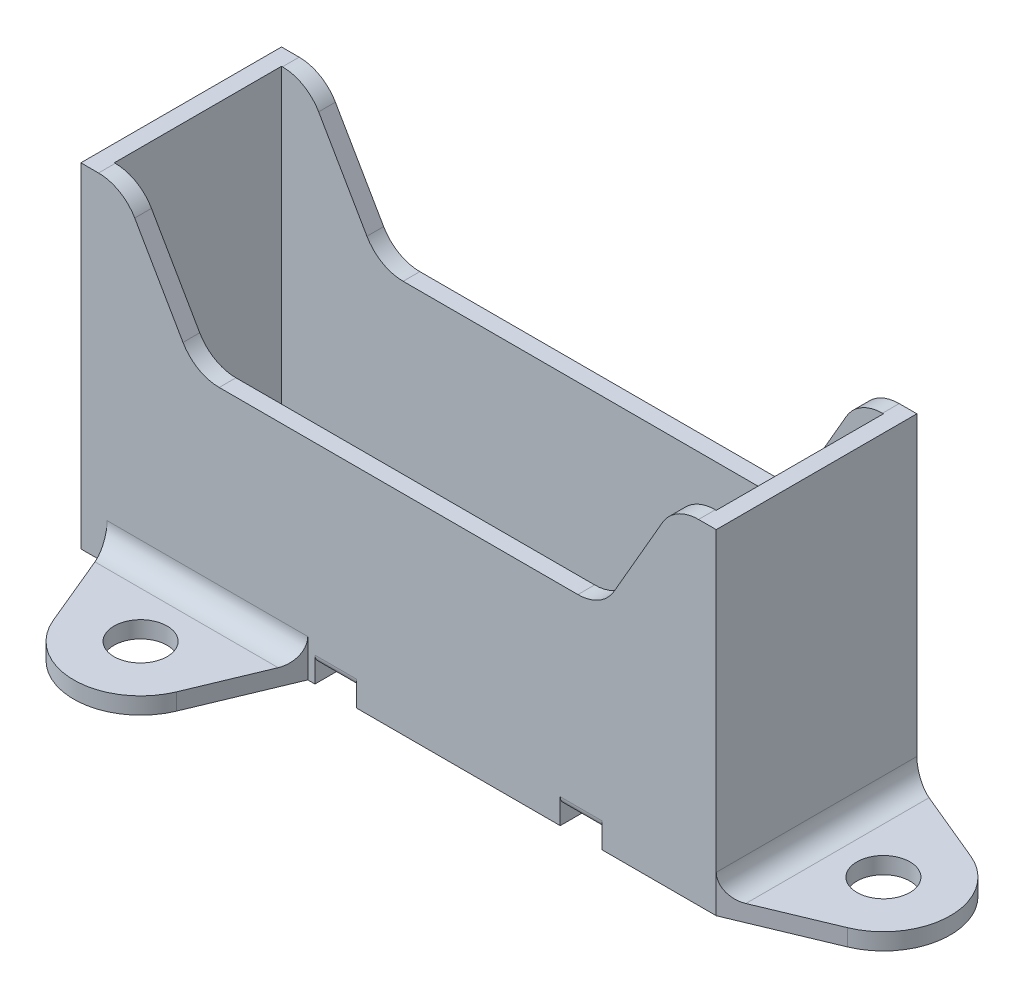
SolidWorks part; units mm, degrees
ref_plane "Front Plane" through (0, 0, 0) normal (0, 0, 1) x (1, 0, 0)
ref_plane "Top Plane" through (0, 0, 0) normal (0, 1, 0) x (1, 0, 0)
ref_plane "Right Plane" through (0, 0, 0) normal (1, 0, 0) x (0, 0, -1)
sketch "Sketch15" plane through (0, 0, 0) normal (0, 1, 0) x (1, 0, 0)
  line L0 (-38, -12) -> (-38, 12)
  line L1 (-36, -10) -> (36, -10)
  line L2 (-36, -10) -> (-36, 10)
  line L3 (-36, 10) -> (36, 10)
  line L4 (36, -10) -> (36, 10)
  line L5 (-36, -10) -> (36, 10) construction
  line L6 (-36, 10) -> (36, -10) construction
  line L7 (-38, 12) -> (38, 12)
  line L8 (38, -12) -> (38, 12)
  line L9 (-38, -12) -> (38, -12)
  point P0 (0, 0)
  dimension "D1" = 72
  dimension "D2" = 20
  dimension "D3" = 2
extrude "Boss-Extrude8" add sketch "Sketch15" along normal blind 38
sketch "Sketch18" plane through (0, 0, 0) normal (0, -1, 0) x (1, 0, 0)
  line L0 (-38, 12) -> (-34.8585, 12)
  line L1 (38, 12) -> (49.0769, 7.3846)
  line L2 (49.0769, -7.3846) -> (38, -12)
  line L3 (38, 12) -> (38, -12) construction
  line L4 (38, -12) -> (-38, -12)
  line L7 (-34.8585, 12) -> (-30.2431, 23.0769)
  line L8 (-38, 12) -> (-38, -12)
  line L9 (-10.8585, 12) -> (-15.4739, 23.0769)
  line L10 (-22.8585, 20) -> (-22.8585, -0.3951) construction
  line L11 (-10.8585, 12) -> (38, 12)
  arc A0 (49.0769, 7.3846) -> (49.0769, -7.3846) centre (46, 0) cw
  arc A2 (-30.2431, 23.0769) -> (-15.4739, 23.0769) centre (-22.8585, 20) cw
  point P17 (-21.2607, 20)
  point P19 (0, 0)
  point P20 (-14.7673, 22.8333)
  point P21 (-25.8796, 20)
  point P22 (-25.026, 20)
  point P23 (0, 0)
  point P24 (-23.2961, 20)
  dimension "D1" = 8
  dimension "D4" = 8
  dimension "D2" = 8
  dimension "D3" = 67.38
  dimension "D5" = 8
  dimension "D6" = 67.38
  dimension "D7" = 71.7042
extrude "Boss-Extrude11" add sketch "Sketch18" along normal blind 2
hole_wizard "1/4 (0.25) Diameter Hole1" positions "Sketch19" profile "Sketch20" hole size "1/4" standard "ANSI Inch" end condition through all
sketch "Sketch19" plane through (0, 0, 0) normal (0, 1, 0) x (1, 0, 0)
  point P8 (46, 0)
  point P10 (46, 0)
  point P15 (-22.8585, -20)
sketch "Sketch20" plane through (46, 0, 0) normal (1, 0, 0) x (0, 0, 1)
  line L0 (0, 0) -> (0, 2)
  line L1 (0, 2) -> (3.175, 2)
  line L2 (3.175, 2) -> (3.175, 0)
  line L5 (3.175, 0) -> (0, 0)
  line L11 (0, -6.35) -> (0, 107.95) construction
  dimension "Thru Hole Dia." = 6.35
  dimension "Thru Hole Depth" = 2
sketch "Sketch21" plane through (0, 0, -12) normal (0, 0, -1) x (-1, 0, 0)
  line L0 (0, -4.7141) -> (0, 50.0572) construction
  line L1 (-33, 38) -> (-24.3397, 23)
  line L2 (-38, 38) -> (38, 38) construction
  line L3 (-24.3397, 23) -> (24.3397, 23)
  line L4 (24.3397, 23) -> (33, 38)
  line L5 (33, 38) -> (-33, 38)
  line L6 (38, -2) -> (-38, -2) construction
  line L7 (-24.3397, -2) -> (-19.3397, -2)
  line L8 (-24.3397, -2) -> (-24.3397, 0)
  line L9 (-24.3397, 0) -> (-19.3397, 0)
  line L10 (-19.3397, -2) -> (-19.3397, 0)
  line L11 (-38, 0) -> (-49.0769, 0) construction
  line L12 (5, -2) -> (10, -2)
  line L13 (5, -2) -> (5, 0)
  line L14 (5, 0) -> (10, 0)
  line L15 (10, -2) -> (10, 0)
  point P19 (0, 0)
  point P23 (0, 0)
  dimension "D1" = 60
  dimension "D2" = 5
  dimension "D3" = 15
  dimension "D4" = 5
  dimension "D5" = 5
  dimension "D6" = 5
extrude "Cut-Extrude1" cut sketch "Sketch21" against normal through all
fillet "Fillet1" radius 5 8 edges at (-33, 38, 11) (33, 38, 11) (-33, 38, -11) (-24.3397, 23, -11) (-24.3397, 23, 11) (24.3397, 23, 11) (33, 38, -11) (24.3397, 23, -11)
fillet "Fillet2" radius 1 8 edges at (21.8397, 0, -12) (21.8397, 0, -10) (21.8397, 0, 10) (21.8397, 0, 12) (-7.5, 0, -12) (-7.5, 0, -10) (-7.5, 0, 10) (-7.5, 0, 12)
fillet "Fillet3" radius 2.5 2 edges at (38, 0, 0) (-22.8585, 0, 12)
